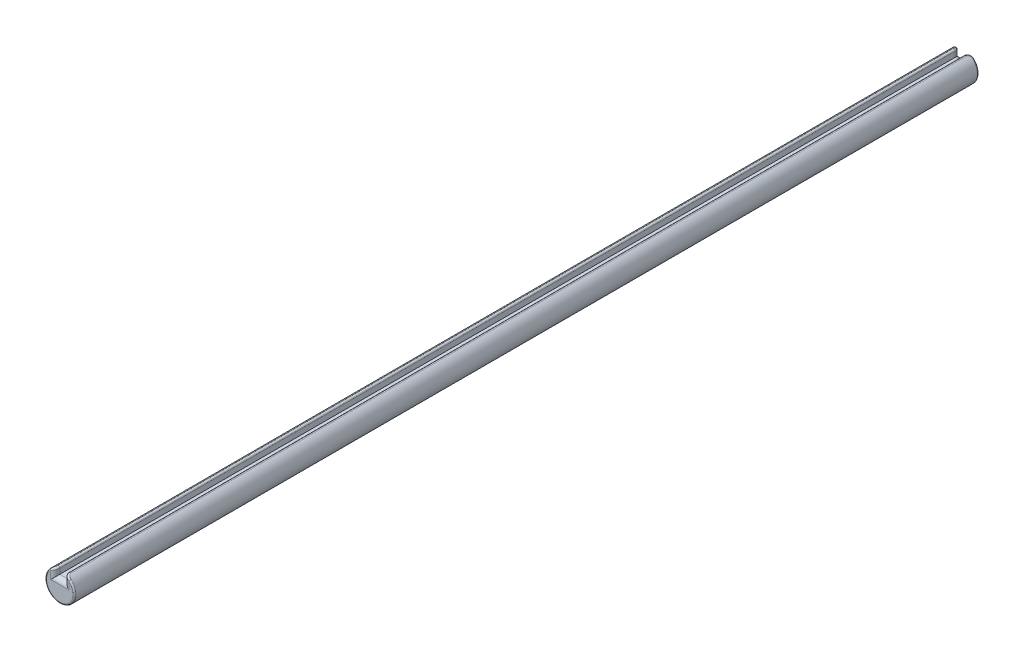
SolidWorks part; units mm, degrees
ref_plane "Front Plane" through (0, 0, 0) normal (0, 0, 1) x (1, 0, 0)
ref_plane "Top Plane" through (0, 0, 0) normal (0, 1, 0) x (1, 0, 0)
ref_plane "Right Plane" through (0, 0, 0) normal (1, 0, 0) x (0, 0, -1)
sketch "Sketch1" plane through (0, 0, 0) normal (0, 0, 1) x (1, 0, 0)
  circle A0 centre (0, 0) radius 4.8625
  dimension "D1" = 9.725
extrude "Boss-Extrude1" add sketch "Sketch1" along normal mid plane 300
sketch "Sketch2" plane through (0, 0, 150) normal (0, 0, 1) x (1, 0, 0)
  line L0 (0, 0) -> (0, 7.2181) construction
  line L2 (1.5, 7.6125) -> (-1.5, 7.6125)
  line L3 (1.5, 7.6125) -> (1.5, 2.1125)
  line L4 (1.5, 2.1125) -> (-1.5, 2.1125)
  line L5 (-1.5, 7.6125) -> (-1.5, 2.1125)
  line L6 (1.5, 7.6125) -> (-1.5, 2.1125) construction
  line L7 (1.5, 2.1125) -> (-1.5, 7.6125) construction
  circle A0 centre (0, 0) radius 4.8625 construction
  point P3 (0, 4.8625)
  point P8 (0, 0)
  dimension "D1" = 5.5
  dimension "D2" = 3
extrude "Cut-Extrude1" cut sketch "Sketch2" against normal up to surface (300 mm away) up to face at (4.8625, 0, -150)
fillet "Fillet1" radius 1.5 6 edges at (-1.5, 3.3689, -150) (1.5, 3.3689, -150) (1.5, 3.3689, 150) (-1.5, 3.3689, 150) (0, 2.1125, 150) (0, 2.1125, -150)
fillet "Fillet2" radius 0.5 8 edges at (2.0638, 4.4028, -149.672) (0, -4.8625, -150) (-1.7947, 4.5192, -149.3928) (-2.0638, 4.4028, 149.672) (0, -4.8625, 150) (1.7947, 4.5192, 149.3928) (-1.5, 4.6254, 0) (1.5, 4.6254, 0)
